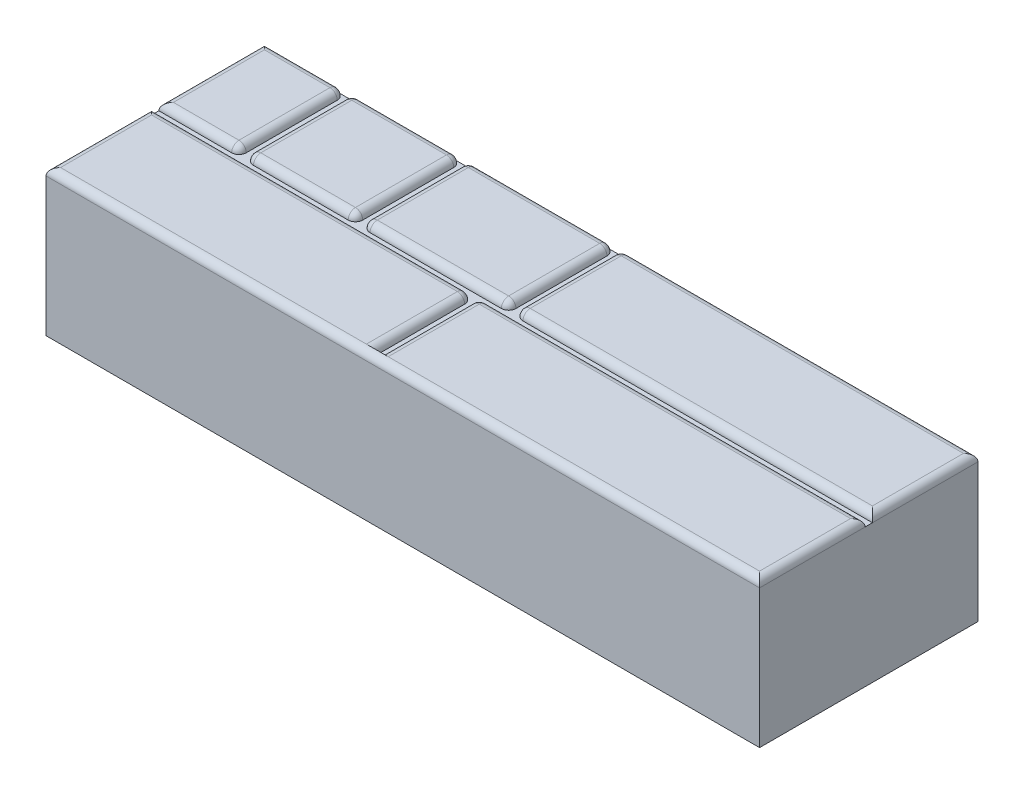
SolidWorks part; units mm, degrees
ref_plane "Front Plane" through (0, 0, 0) normal (0, 0, 1) x (1, 0, 0)
ref_plane "Top Plane" through (0, 0, 0) normal (0, 1, 0) x (1, 0, 0)
ref_plane "Right Plane" through (0, 0, 0) normal (1, 0, 0) x (0, 0, -1)
sketch "Sketch1" plane through (0, 0, 0) normal (0, 1, 0) x (1, 0, 0)
  line L1 (490, -150) -> (-490, -150)
  line L2 (490, -150) -> (490, 150)
  line L3 (490, 150) -> (-490, 150)
  line L4 (-490, -150) -> (-490, 150)
  line L5 (490, -150) -> (-490, 150) construction
  line L6 (490, 150) -> (-490, -150) construction
  point P0 (0, 0)
extrude "Boss-Extrude1" add sketch "Sketch1" along normal blind 200
sketch "Sketch2" plane through (0, 200, 0) normal (0, 1, 0) x (1, 0, 0)
  line L0 (0, 0) -> (0, 5) construction
  line L1 (0, 0) -> (0, -5) construction
  line L2 (0, -5) -> (490, -5)
  line L3 (490, -150) -> (490, 150) construction
  line L4 (490, -5) -> (490, 5)
  line L5 (490, 5) -> (-490, 5)
  line L6 (-490, 150) -> (-490, -150) construction
  line L7 (-490, 5) -> (-490, -5)
  line L8 (-490, -5) -> (0, -5)
extrude "Cut-Extrude1" cut sketch "Sketch2" against normal blind 10
fillet "Fillet1" radius 10 8 edges at (490, 200, 77.5) (490, 200, -77.5) (0, 200, -150) (0, 200, 150) (0, 200, -5) (0, 200, 5) (-490, 200, -77.5) (-490, 200, 77.5)
sketch "Sketch3" plane through (0, 200, 0) normal (0, 1, 0) x (1, 0, 0)
  line L0 (-480, 5) -> (-380, 5) construction
  line L2 (-380, 5) -> (-370, 5)
  line L3 (-370, 5) -> (-370, 150)
  line L5 (-370, 150) -> (-380, 150)
  line L6 (-380, 150) -> (-380, 5)
  line L7 (-370, 5) -> (-220, 5) construction
  line L8 (-220, 5) -> (-210, 5)
  line L9 (-210, 5) -> (-210, 150)
  line L12 (-220, 150) -> (-220, 5)
  line L13 (-210, 5) -> (-9.5964, 5) construction
  line L14 (-9.5964, 5) -> (-9.5964, 150)
  line L15 (-9.5964, 150) -> (0, 150)
  line L16 (0, 150) -> (0, 5)
  line L17 (0, 5) -> (-9.5964, 5)
  line L18 (-220, 150) -> (-210, 150)
  line L20 (-50, -5) -> (-50, -140)
  line L21 (-480, -140) -> (480, -140) construction
  line L22 (-50, -140) -> (-40, -140)
  line L23 (-40, -140) -> (-40, -5)
  line L24 (-40, -5) -> (-50, -5)
extrude "Cut-Extrude2" cut sketch "Sketch3" against normal blind 10
fillet "Fillet2" radius 10 22 edges at (-50, 200, 77.5) (-40, 200, 77.5) (0, 200, -77.5) (-9.5964, 200, -77.5) (-210, 200, -77.5) (-380, 200, -77.5) (-220, 200, -77.5) (-370, 200, -77.5) (-50, 197.0711, 7.9289) (-40, 197.0711, 7.9289) (0, 197.0711, -7.9289) (0, 197.0711, -147.0711) (-9.5964, 197.0711, -147.0711) (-9.5964, 197.0711, -7.9289) (-210, 197.0711, -7.9289) (-210, 197.0711, -147.0711) (-380, 197.0711, -147.0711) (-380, 197.0711, -7.9289) (-220, 197.0711, -147.0711) (-220, 197.0711, -7.9289) (-370, 197.0711, -7.9289) (-370, 197.0711, -147.0711)
